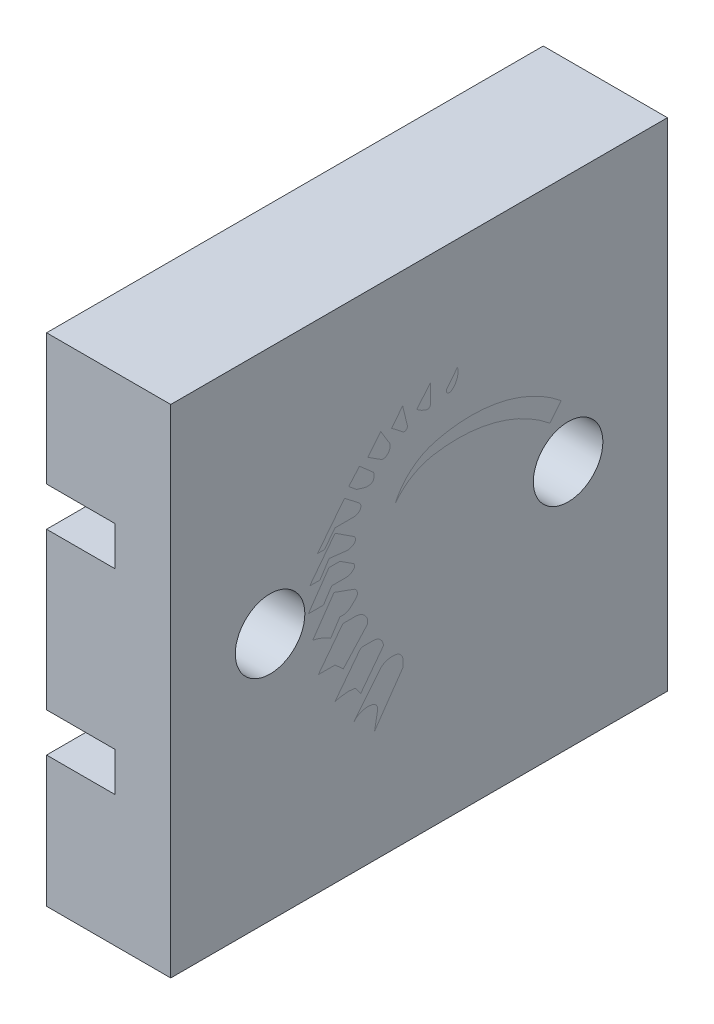
SolidWorks part; units mm, degrees
material "Nylon 101"
ref_plane "Front Plane" through (0, 0, 0) normal (0, 0, 1) x (1, 0, 0)
ref_plane "Top Plane" through (0, 0, 0) normal (0, 1, 0) x (1, 0, 0)
ref_plane "Right Plane" through (0, 0, 0) normal (1, 0, 0) x (0, 0, -1)
sketch "Sketch1" plane through (0, 0, 0) normal (1, 0, 0) x (0, 0, -1)
  line L1 (-6.35, 6.35) -> (6.35, 6.35)
  line L2 (-6.35, 6.35) -> (-6.35, -6.35)
  line L3 (-6.35, -6.35) -> (6.35, -6.35)
  line L4 (6.35, 6.35) -> (6.35, -6.35)
  line L5 (-6.35, 6.35) -> (6.35, -6.35) construction
  line L6 (-6.35, -6.35) -> (6.35, 6.35) construction
  point P0 (0, 0)
  dimension "D1" = 12.7
extrude "Boss-Extrude1" add sketch "Sketch1" along normal blind 3.175
sketch "Sketch2" plane through (0, -6.35, 0) normal (0, -1, 0) x (1, 0, 0)
  line L0 (0, 0) -> (3.175, 0) construction
  line L1 (0, 6.35) -> (0, -6.35) construction
  line L2 (3.175, 6.35) -> (3.175, -6.35) construction
  circle A0 centre (0, 0) radius 1.1906
  dimension "D1" = 2.3813
extrude "Cut-Extrude1" cut sketch "Sketch2" against normal blind 12
sketch "Sketch3" plane through (0, -6.35, 0) normal (0, -1, 0) x (1, 0, 0)
  circle A0 centre (0, 0) radius 2
  dimension "D1" = 4
extrude "Cut-Extrude2" cut sketch "Sketch3" against normal blind 2
hole_wizard "Tap Drill for #2-56 Tap1" positions "3DSketch1" profile "Sketch4" hole size "#2-56" standard "ANSI Inch"
sketch3d "3DSketch1"
  line L0 (0, 6.35, 0) -> (0, -6.35, 0) construction
  line L1 (0, 6.35, -6.35) -> (0, 6.35, 6.35) construction
  line L2 (0, -4.35, 0) -> (0, -6.35, 0) construction
  line L4 (0, 0, -6.35) -> (0, 0, 6.35) construction
  line L5 (0, -6.35, -6.35) -> (0, 6.35, -6.35) construction
  line L6 (0, 6.35, 6.35) -> (0, -6.35, 6.35) construction
  point P0 (0, 0, -3.81)
  point P2 (0, 0, 3.81)
  dimension "D1" = 7.62
  dimension "D2" = 3.81
sketch "Sketch4" plane through (0, 0, -3.81) normal (0, 1, 0) x (0, 0, 1)
  line L0 (0, 0) -> (0, 12.9842)
  line L1 (0, 12.9842) -> (0.889, 12.45)
  line L2 (0.889, 12.45) -> (0.889, 0)
  line L5 (0.889, 0) -> (0, 0)
  line L10 (0, 12.9842) -> (-0.889, 12.45) construction
  line L11 (0, -6.35) -> (0, 107.95) construction
  dimension "Hole Dia." = 1.778
  dimension "Hole Depth" = 12.45
  dimension "Drill Angle" = 118
sketch "Sketch5" plane through (0, 0, 6.35) normal (0, 0, 1) x (1, 0, 0)
  line L0 (0, 0) -> (3.175, 0) construction
  line L1 (0, 6.35) -> (0, -6.35) construction
  line L2 (3.175, 6.35) -> (3.175, -6.35) construction
  line L3 (3.175, 0) -> (3.175, 6.35) construction
  line L5 (3.175, 6.35) -> (0, 6.35) construction
  line L6 (0, 3) -> (1.75, 3)
  line L7 (0, 3) -> (0, 2)
  line L8 (0, 2) -> (1.75, 2)
  line L9 (1.75, 3) -> (1.75, 2)
  line L10 (0, 3) -> (1.75, 2) construction
  line L11 (0, 2) -> (1.75, 3) construction
  line L12 (1.75, -3) -> (1.75, -2)
  line L13 (0, -2) -> (1.75, -2)
  line L14 (0, -3) -> (0, -2)
  line L15 (0, -3) -> (1.75, -3)
  point P10 (0.875, 2.5)
  dimension "D1" = 1.75
  dimension "D2" = 1
  dimension "D3" = 2.5
extrude "Cut-Extrude3" cut sketch "Sketch5" against normal through all
sketch "Sketch7" plane through (3.175, 0, 0) normal (1, 0, 0) x (0, 0, -1)
  line L0 (0.6958, 3.1472) -> (0.9808, 3.5083)
  line L1 (3.3451, 1.0879) -> (3.6347, 1.4427)
  line L2 (0.2908, 3.5083) -> (-0.0594, 3.0976)
  line L3 (0.2908, 3.035) -> (0.2908, 3.5083)
  line L4 (-0.4203, 3.3567) -> (-0.6999, 2.9979)
  line L5 (-0.6999, 2.9979) -> (-0.4203, 2.7801)
  line L6 (-0.2993, 2.856) -> (-0.4203, 3.3567)
  line L7 (-0.9804, 3.0665) -> (-1.3076, 2.6575)
  line L8 (-1.3076, 2.6575) -> (-0.9804, 2.449)
  line L9 (-0.776, 2.7271) -> (-0.9804, 3.0665)
  line L10 (-1.5248, 2.5698) -> (-1.7982, 2.257)
  line L11 (-1.7982, 2.257) -> (-1.5991, 2.0932)
  line L12 (-1.5991, 2.0932) -> (-1.4105, 2.0342)
  line L13 (-1.1669, 2.257) -> (-1.5248, 2.5698)
  line L14 (-1.9059, 2.0519) -> (-2.5964, 1.1714)
  line L15 (-2.5964, 1.1714) -> (-2.42, 1.1714)
  line L16 (-2.42, 1.1714) -> (-2.1482, 1.518)
  line L17 (-2.1482, 1.518) -> (-1.6724, 1.518)
  line L18 (-1.5284, 1.7559) -> (-1.9059, 2.0519)
  line L19 (-2.7971, 0.5538) -> (-2.1482, 1.3974)
  line L20 (-2.1482, 1.3974) -> (-1.6724, 1.0879)
  line L21 (-1.8215, 0.8585) -> (-2.3005, 0.9144)
  line L22 (-2.3005, 0.9144) -> (-2.5349, 0.5538)
  line L23 (-2.5349, 0.5538) -> (-2.7971, 0.5538)
  line L24 (-2.8324, -0.0453) -> (-2.4447, -0.0453)
  line L25 (-2.4447, -0.0453) -> (-2.2352, 0.2767)
  line L26 (-2.2352, 0.2767) -> (-1.8728, 0.2767)
  line L27 (-1.6724, 0.4862) -> (-2.0232, 0.7144)
  line L28 (-2.0232, 0.7144) -> (-2.304, 0.7144)
  line L29 (-2.304, 0.7144) -> (-2.8324, -0.0453)
  line L30 (-2.1742, 0.0999) -> (-2.7176, -0.6873)
  line L31 (-2.1742, 0.0999) -> (-1.6724, -0.0815)
  line L32 (-2.2605, -0.8734) -> (-2.0232, -0.5143)
  line L33 (-1.5991, -0.2934) -> (-1.7382, -0.4289)
  line L34 (-2.5747, -1.5183) -> (-1.9489, -0.7028)
  line L35 (-1.9489, -0.7028) -> (-1.6274, -0.7028)
  line L36 (-1.3201, -0.9082) -> (-1.3201, -1.0308)
  line L37 (-1.3201, -1.0308) -> (-1.937, -1.7114)
  line L38 (-1.937, -1.7114) -> (-2.1482, -1.52)
  line L39 (-2.1482, -1.52) -> (-2.5747, -1.5183)
  line L41 (-1.5284, -1.52) -> (-2.1482, -2.3269)
  line L42 (-0.9109, -1.7114) -> (-1.4941, -2.4814)
  line L43 (-1.4105, -1.4664) -> (-1.1669, -1.4664)
  line L44 (-1.4941, -2.4814) -> (-1.6274, -2.2949)
  line L45 (-2.1482, -2.3269) -> (-1.9964, -2.2949)
  line L46 (-1.6274, -2.2949) -> (-1.7982, -2.2736)
  line L47 (-1.7982, -2.2736) -> (-1.9964, -2.2949)
  line L48 (-1.6724, -3.027) -> (-1.0146, -2.2083)
  line L49 (-0.4104, -2.2627) -> (-0.4104, -2.4389)
  line L50 (-0.4104, -2.4389) -> (-1.1386, -3.4919)
  line L51 (-1.1386, -3.4919) -> (-1.0622, -3.0714)
  arc A0 (-1.6724, 1.0879) -> (-1.6724, 0.9144) centre (-1.7288, 1.0011) cw
  arc A1 (0.9808, 3.5083) -> (0.9808, 3.2935) centre (0.5794, 3.4009) cw
  arc A2 (0.9808, 3.2935) -> (0.8267, 3.0665) centre (0.5775, 3.4014) cw
  arc A3 (0.8267, 3.0665) -> (0.6958, 3.1472) centre (0.7773, 3.1329) cw
  arc A4 (3.6347, 1.4427) -> (0.414, 2.1481) centre (1.3282, -1.3828) ccw
  arc A5 (0.414, 2.1481) -> (-0.6172, 1.2763) centre (0.8043, 0.6407) ccw
  arc A6 (3.3451, 1.0879) -> (0.3441, 1.87) centre (0.9913, -1.7955) ccw
  arc A7 (0.3441, 1.87) -> (-0.6172, 1.2763) centre (0.6099, 0.3644) ccw
  arc A8 (-0.0594, 3.0976) -> (0.1917, 2.9619) centre (0.3837, 3.6173) ccw
  arc A9 (0.1917, 2.9619) -> (0.2908, 3.035) centre (0.2134, 3.0362) ccw
  arc A10 (-0.4203, 2.7801) -> (-0.2993, 2.856) centre (-0.3736, 2.84) ccw
  arc A11 (-0.9804, 2.449) -> (-0.8414, 2.449) centre (-0.9109, 2.558) ccw
  arc A12 (-0.8414, 2.449) -> (-0.7391, 2.6044) centre (-0.9636, 2.6407) ccw
  arc A13 (-0.7391, 2.6044) -> (-0.776, 2.7271) centre (-0.8839, 2.6278) ccw
  arc A14 (-1.4105, 2.0342) -> (-1.2297, 2.0342) centre (-1.3201, 2.3235) ccw
  arc A15 (-1.2297, 2.0342) -> (-1.1669, 2.0932) centre (-1.2591, 2.1285) ccw
  arc A16 (-1.1669, 2.0932) -> (-1.1669, 2.257) centre (-1.3806, 2.1751) ccw
  arc A17 (-1.6724, 1.518) -> (-1.5284, 1.5734) centre (-1.6724, 1.7326) ccw
  arc A18 (-1.5284, 1.5734) -> (-1.5284, 1.7559) centre (-1.6109, 1.6647) ccw
  arc A19 (-1.6724, 0.9144) -> (-1.8215, 0.8585) centre (-1.8728, 1.2226) cw
  arc A20 (-1.8728, 0.2767) -> (-1.6724, 0.3644) centre (-1.8728, 0.5496) ccw
  arc A21 (-1.6724, 0.3644) -> (-1.6724, 0.4862) centre (-1.7382, 0.4253) ccw
  arc A22 (-1.6724, -0.0815) -> (-1.5991, -0.2934) centre (-1.7214, -0.2171) cw
  arc A23 (-1.7382, -0.4289) -> (-2.0232, -0.5143) centre (-1.9626, -0.1983) cw
  arc A24 (-2.2605, -0.8734) -> (-2.7176, -0.6873) centre (-2.9551, -1.9249) ccw
  arc A25 (-1.6274, -0.7028) -> (-1.3201, -0.9082) centre (-1.6274, -1.0354) cw
  arc A26 (-1.5284, -1.52) -> (-1.4105, -1.4664) centre (-1.4192, -1.6039) cw
  arc A27 (-1.1669, -1.4664) -> (-0.9109, -1.7114) centre (-1.1669, -1.7226) cw
  arc A28 (-1.0146, -2.2083) -> (-0.7391, -2.0633) centre (-0.7098, -2.4532) cw
  arc A29 (-0.7391, -2.0633) -> (-0.6172, -2.0633) centre (-0.6782, -2.8731) cw
  arc A30 (-0.6172, -2.0633) -> (-0.4104, -2.2627) centre (-0.6341, -2.2878) cw
  arc A31 (-1.0622, -3.0714) -> (-1.1928, -2.8747) centre (-1.2299, -3.041) ccw
  arc A32 (-1.6724, -3.027) -> (-1.4263, -2.8747) centre (-1.3336, -3.2992) cw
  arc A33 (-1.1928, -2.8747) -> (-1.4263, -2.8747) centre (-1.3096, -3.3986) ccw
wrap "Wrap1" sketch "Sketch7" wrap type scribe source sketch "Sketch7" face at (3.175, 0, -4.699)
